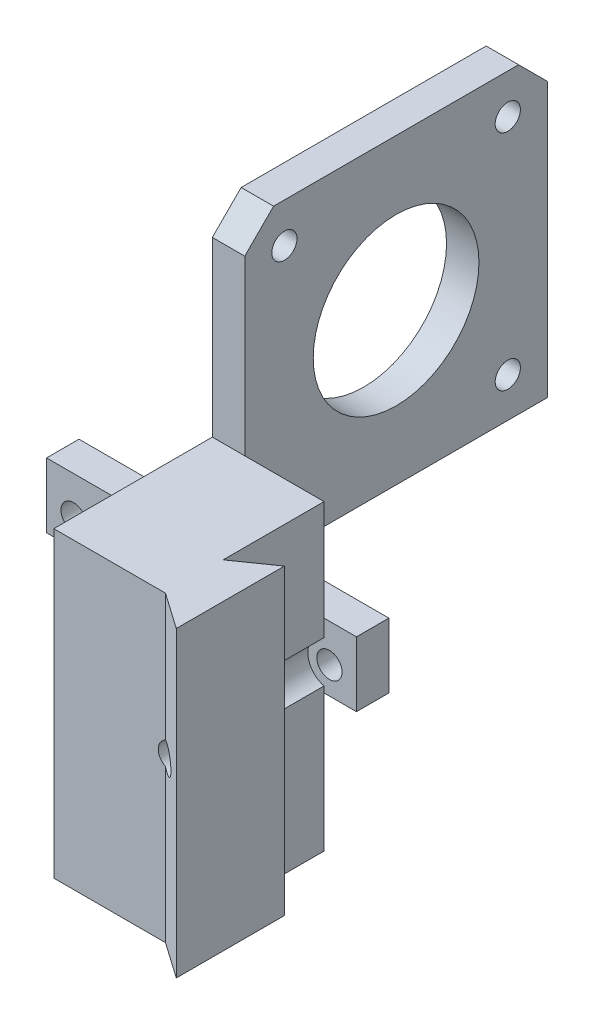
SolidWorks part; units mm, degrees
ref_plane "前视基准面" through (0, 0, 0) normal (0, 0, 1) x (1, 0, 0)
ref_plane "上视基准面" through (0, 0, 0) normal (0, 1, 0) x (1, 0, 0)
ref_plane "右视基准面" through (0, 0, 0) normal (1, 0, 0) x (0, 0, -1)
sketch "草图1" plane through (0, 0, 0) normal (0, 0, 1) x (1, 0, 0)
  line L0 (0, 4.5) -> (0, -4.5) construction
  line L1 (-21.5, -4.5) -> (21.5, -4.5)
  line L2 (-21.5, -4.5) -> (-21.5, 4.5)
  line L3 (-21.5, 4.5) -> (21.5, 4.5)
  line L4 (21.5, -4.5) -> (21.5, 4.5)
  line L5 (-21.5, -4.5) -> (21.5, 4.5) construction
  line L6 (-21.5, 4.5) -> (21.5, -4.5) construction
  circle A0 centre (-17.75, -0.75) radius 1.75
  circle A1 centre (17.75, -0.75) radius 1.75
  point P0 (0, 0)
  dimension "D3" = 3.5
  dimension "D4" = 3.75
  dimension "D5" = 3.75
  dimension "D1" = 9
  dimension "D2" = 43
extrude "凸台-拉伸1" add sketch "草图1" along normal blind 4.5
sketch "草图2" plane through (0, 0, 4.5) normal (0, 0, 1) x (1, 0, 0)
  line L5 (21.5, 4.5) -> (-21.5, 4.5) construction
  line L6 (1.5, 4.5) -> (6, 4.5)
  line L7 (1.5, 4.5) -> (1.5, 46.5)
  line L8 (1.5, 46.5) -> (6, 46.5)
  line L9 (6, 4.5) -> (6, 46.5)
  line L10 (-21.5, 4.5) -> (-21.5, -4.5) construction
  dimension "D1" = 42
  dimension "D2" = 4.5
  dimension "D3" = 23
extrude "凸台-拉伸2" add sketch "草图2" against normal blind 42
sketch "草图3" plane through (6, 0, 0) normal (1, 0, 0) x (0, 0, -1)
  line L0 (-4.5, 25.5) -> (37.5, 25.5) construction
  line L1 (37.5, 46.5) -> (-4.5, 46.5) construction
  line L2 (37.5, 46.5) -> (-4.5, 4.5) construction
  line L3 (33.5, 46.5) -> (37.5, 42.5)
  line L4 (37.5, 4.5) -> (37.5, 46.5) construction
  line L5 (-4.5, 4.5) -> (-4.5, 46.5) construction
  line L6 (16.5, 46.5) -> (16.5, 4.5) construction
  line L7 (37.5, 4.5) -> (0, 4.5) construction
  line L8 (-0.5, 46.5) -> (-4.5, 42.5)
  line L9 (-4.5, 46.5) -> (37.5, 4.5) construction
  line L10 (-4.5, 42.5) -> (-4.5, 46.5)
  line L11 (-4.5, 46.5) -> (-0.5, 46.5)
  line L12 (33.5, 46.5) -> (37.5, 46.5)
  line L13 (37.5, 46.5) -> (37.5, 42.5)
  circle A0 centre (16.5, 25.5) radius 11.5
  circle A1 centre (32, 41) radius 1.75
  circle A2 centre (32, 10) radius 1.75
  circle A3 centre (1, 10) radius 1.75
  circle A4 centre (1, 41) radius 1.75
  dimension "D3" = 23
  dimension "D4" = 3.5
  dimension "D5" = 31
  dimension "D1" = 4
  dimension "D2" = 4
extrude "切除-拉伸2" cut sketch "草图3" against normal blind 4.5
sketch "草图11" plane through (0, 4.5, 0) normal (0, 1, 0) x (1, 0, 0)
  line L0 (22, -15) -> (22, -30)
  line L1 (17, -18.5) -> (17, -26.5)
  line L2 (17, -22.5) -> (22, -22.5) construction
  line L3 (17, -18.5) -> (22, -15)
  line L4 (17, -26.5) -> (22, -30)
  line L6 (21.5, -4.5) -> (6, -4.5) construction
  line L7 (1.5, -4.5) -> (-21.5, -4.5) construction
  line L8 (17, -26.5) -> (7, -26.5)
  line L9 (17, -26.5) -> (17, -4.5)
  line L10 (17, -4.5) -> (7, -4.5)
  line L11 (7, -26.5) -> (7, -4.5)
  line L12 (-21.5, -4.5) -> (-21.5, 0) construction
  line L13 (1.5, -4.5) -> (7, -4.5)
  line L14 (1.5, -4.5) -> (1.5, -26.5)
  line L15 (1.5, -26.5) -> (7, -26.5)
  line L16 (7, -4.5) -> (7, -26.5)
  point P6 (22, -22.5)
  dimension "D1" = 15
  dimension "D2" = 8
  dimension "D3" = 5
  dimension "D4" = 28.5
  dimension "D5" = 18
  dimension "D6" = 10
extrude "凸台-拉伸10" add sketch "草图11" along normal blind 14 and the other way blind 28 contours L1 L2 L0 L3 | L11 L8 L9 L1 L10 | L2 L9 L4 L0 | L14 L13 L16 L15 region at (19.7536, 4.5, 19.5362) region at (19.7536, 4.5, 25.4638) region at (12, 4.5, 15.5)
extrude "切除-拉伸7" cut sketch "草图1<6>" along normal through all contours A1 region at (17.75, -0.75, 0)
sketch "草图1<6>" plane through (0, 0, 0) normal (0, 0, 1) x (1, 0, 0) same geometry as "草图1"
sketch "草图12" plane through (0, 0, 0) normal (0, 0, -1) x (-1, 0, 0)
  circle A0 centre (-17.75, -0.75) radius 3
  dimension "D1" = 6
extrude "切除-拉伸8" cut sketch "草图12" against normal blind 14 from surface starting at face at (18.9167, -0.25, 4.5)
